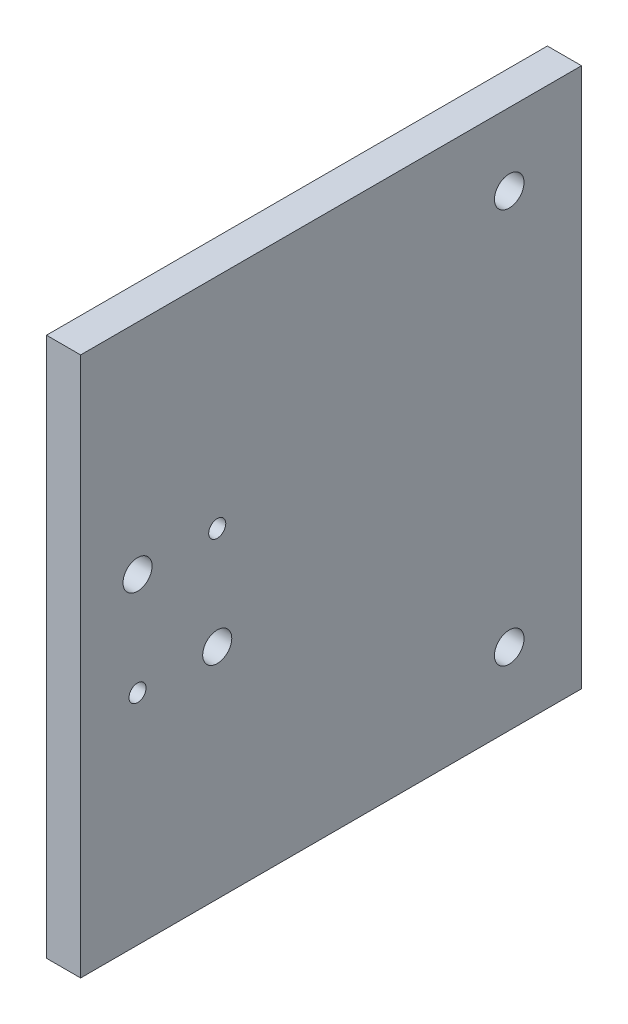
SolidWorks part; units mm, degrees
ref_plane "Front Plane" through (0, 0, 0) normal (1, 0, 0) x (0, 1, 0)
ref_plane "Top Plane" through (0, 0, 0) normal (0, 0, 1) x (0, 1, 0)
ref_plane "Right Plane" through (0, 0, 0) normal (0, 1, 0) x (-1, 0, 0)
sketch "Sketch1" plane through (0, 0, 0) normal (1, 0, 0) x (0, 1, 0)
  line L0 (0, 25) -> (0, -25) construction
  line L1 (-47.4, -25) -> (47.4, -25) construction
  line L2 (-47.4, -25) -> (-47.4, 25) construction
  line L3 (-47.4, 25) -> (47.4, 25) construction
  line L4 (47.4, -25) -> (47.4, 25) construction
  line L5 (-47.4, -25) -> (47.4, 25) construction
  line L6 (-47.4, 25) -> (47.4, -25) construction
  line L7 (-47.4, 16) -> (47.4, 16) construction
  line L8 (-9, -7) -> (9, -7) construction
  line L9 (-9, -7) -> (-9, 7) construction
  line L10 (-9, 7) -> (9, 7) construction
  line L11 (9, -7) -> (9, 7) construction
  line L12 (-9, -7) -> (9, 7) construction
  line L13 (-9, 7) -> (9, -7) construction
  line L14 (-34.7, -15) -> (34.7, -15) construction
  line L15 (-34.7, -15) -> (-34.7, 15) construction
  line L16 (-34.7, 15) -> (34.7, 15) construction
  line L17 (34.7, -15) -> (34.7, 15) construction
  line L18 (-34.7, -15) -> (34.7, 15) construction
  line L19 (-34.7, 15) -> (34.7, -15) construction
  line L20 (-47.4, -25) -> (47.4, -25) construction
  line L21 (-47.4, -25) -> (-47.4, -71)
  line L22 (-47.4, -71) -> (47.4, -71)
  line L23 (47.4, -25) -> (47.4, -71) construction
  line L24 (-47.4, -71) -> (-34.7, -71) construction
  line L25 (-47.4, -71) -> (-47.4, -58.3) construction
  line L26 (-47.4, -58.3) -> (-34.7, -58.3) construction
  line L27 (-34.7, -71) -> (-34.7, -58.3) construction
  line L28 (47.4, -71) -> (34.7, -71) construction
  line L29 (47.4, -71) -> (47.4, -58.3) construction
  line L30 (47.4, -58.3) -> (34.7, -58.3) construction
  line L31 (34.7, -71) -> (34.7, -58.3) construction
  line L32 (47.4, -25) -> (47.4, 16) construction
  line L33 (-47.4, 16) -> (-47.4, -25)
  line L34 (47.4, -71) -> (47.4, 17)
  line L35 (47.4, 16) -> (147.4, 16) construction
  line L36 (47.4, 16) -> (47.4, -71) construction
  line L39 (-47.4, 16) -> (147.4, 16) construction
  line L40 (-47.4, 16) -> (-47.4, 17)
  line L43 (-47.4, 17) -> (47.4, 17)
  line L44 (-47.4, -45.6) -> (47.4, -45.6) construction
  circle A0 centre (-9, 7) radius 1.5
  circle A1 centre (-9, -7) radius 2.555
  circle A2 centre (9, -7) radius 1.5
  circle A3 centre (9, 7) radius 2.555
  circle A4 centre (-34.7, 15) radius 2.555 construction
  circle A5 centre (-34.7, -15) radius 2.555 construction
  circle A6 centre (34.7, 15) radius 2.555 construction
  circle A7 centre (34.7, -15) radius 2.555 construction
  circle A8 centre (-34.7, -58.3) radius 2.6
  circle A9 centre (34.7, -58.3) radius 2.6
  point P0 (0, 0)
  point P8 (0, 0)
  point P17 (0, 0)
  dimension "D5" = 5.11
  dimension "D6" = 3
  dimension "D9" = 5.11
  dimension "D10" = 5.11
  dimension "D11" = 5.11
  dimension "D12" = 3
  dimension "D13" = 3
  dimension "D17" = 5.2
  dimension "D18" = 9
  dimension "D20" = 10
  dimension "D1" = 14
  dimension "D2" = 18
  dimension "D3" = 94.8
  dimension "D4" = 50
  dimension "D7" = 12.7
  dimension "D8" = 30
  dimension "D14" = 38.6
  dimension "D15" = 12.7
  dimension "D16" = 12.7
  dimension "D19" = 25.4
extrude "Boss-Extrude1" add sketch "Sketch1" along normal blind 6
